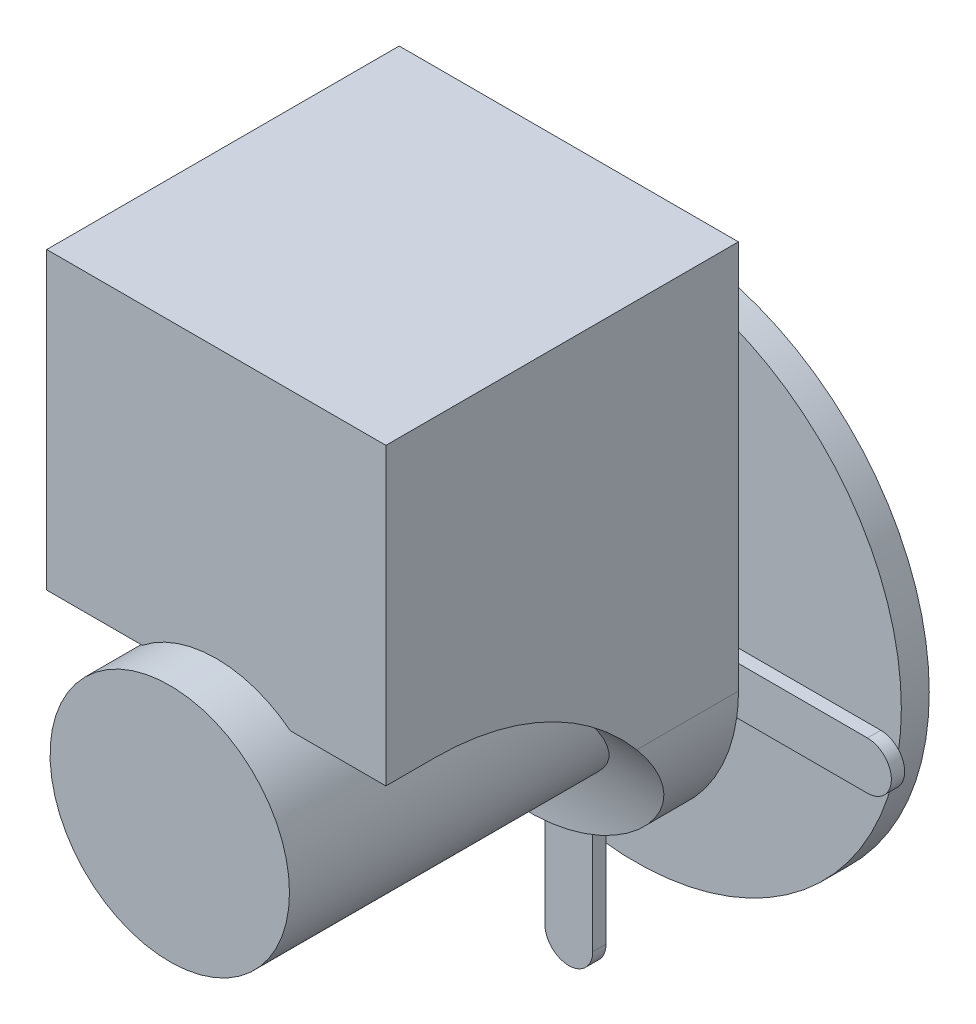
SolidWorks part; units mm, degrees
ref_plane "Front Plane" through (0, 0, 0) normal (0, 0, 1) x (1, 0, 0)
ref_plane "Top Plane" through (0, 0, 0) normal (0, 1, 0) x (1, 0, 0)
ref_plane "Right Plane" through (0, 0, 0) normal (1, 0, 0) x (0, 0, -1)
sketch "Sketch2" plane through (0, 0, 0) normal (0, 0, 1) x (1, 0, 0)
  circle A0 centre (0, 0) radius 18
  dimension "D1" = 36
extrude "Boss-Extrude1" add sketch "Sketch2" along normal blind 60 contours A0
sketch "Sketch3" plane through (0, 0, 0) normal (0, 0, 1) x (1, 0, 0)
  line L1 (-25.5, 0) -> (-25.5, 58.5)
  line L2 (-25.5, 58.5) -> (25.5, 58.5)
  line L3 (25.5, 58.5) -> (25.5, 0)
  arc A0 (-25.5, 0) -> (25.5, 0) centre (0, 0) ccw
  dimension "D1" = 51
extrude "Boss-Extrude2" add sketch "Sketch3" along normal blind 53
sketch "Sketch4" plane through (0, 0, 0) normal (0, 0, 1) x (1, 0, 0)
  line L1 (-3.6, 19.0274) -> (-19.0274, 3.6)
  line L3 (-3.6, -19.0274) -> (-19.0274, -3.6)
  line L4 (3.6, -19.0274) -> (19.0274, -3.6)
  line L5 (3.6, 19.0274) -> (19.0274, 3.6)
  line L6 (3.6, 19.0274) -> (3.6, 44.9)
  line L7 (44.9, 3.6) -> (19.0274, 3.6)
  line L8 (44.9, -3.6) -> (19.0274, -3.6)
  line L9 (-19.0274, 3.6) -> (-44.9, 3.6)
  line L10 (-3.6, 19.0274) -> (-3.6, 44.9)
  line L11 (-19.0274, -3.6) -> (-44.9, -3.6)
  line L14 (3.6, -44.9) -> (3.6, -19.0274)
  line L15 (-3.6, -44.9) -> (-3.6, -19.0274)
  arc A0 (-44.9, 3.6) -> (-44.9, -3.6) centre (-44.9, 0) ccw
  arc A1 (44.9, 3.6) -> (44.9, -3.6) centre (44.9, 0) cw
  arc A2 (-3.6, 44.9) -> (3.6, 44.9) centre (0, 44.9) cw
  arc A3 (-3.6, -44.9) -> (3.6, -44.9) centre (0, -44.9) ccw
  point P0 (-3.6, 19.0274)
  point P2 (3.6, 19.0274)
  point P6 (19.0274, 3.6)
  point P8 (19.0274, -3.6)
  point P9 (3.6, -19.0274)
  point P10 (-3.6, -19.0274)
  point P12 (-19.0274, -3.6)
  point P17 (-19.0274, 3.6)
extrude "Boss-Extrude3" add sketch "Sketch4" against normal blind 2
sketch "Sketch5" plane through (0, 0, 0) normal (1, 0, 0) x (0, 0, -1)
  line L0 (-53, 18) -> (-53, -18) construction
  line L5 (-53, 14.1473) -> (-45.6473, 14.1473)
  line L6 (-53, 14.1473) -> (-53, -25.5)
  line L7 (-53, -25.5) -> (-6, -25.5)
  arc A1 (-6, -25.5) -> (-45.6473, 14.1473) centre (-45.6473, -25.5) ccw
extrude "Cut-Extrude3" cut sketch "Sketch5" against normal through all both and the other way through all
sketch "Sketch6" plane through (0, 0, 60) normal (0, 0, 1) x (1, 0, 0)
  circle A0 centre (0, 0) radius 18 construction
  circle A1 centre (0, 0) radius 18
extrude "Boss-Extrude4" add sketch "Sketch6" against normal blind 56
sketch "Sketch8" plane through (0, 0, 0) normal (0, 0, 1) x (1, 0, 0)
  circle A0 centre (0, 0) radius 3.017
extrude "Boss-Extrude5" add sketch "Sketch8" against normal blind 10
sketch "Sketch9" plane through (0, 0, -10) normal (0, 0, -1) x (-1, 0, 0)
  circle A0 centre (0, 0) radius 40
  dimension "D1" = 80
extrude "Boss-Extrude6" add sketch "Sketch9" along normal blind 4.2
